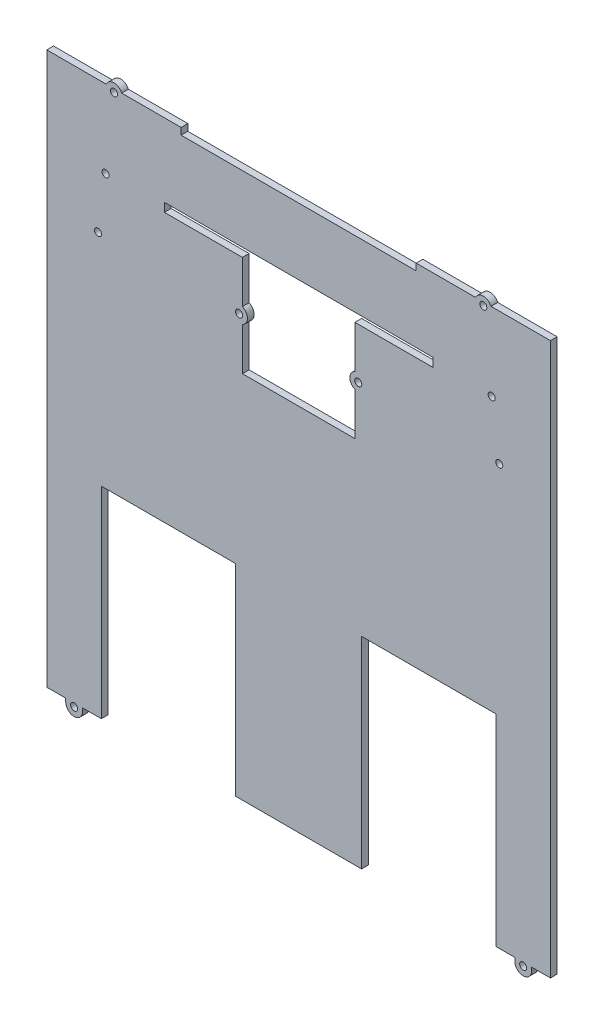
SolidWorks part; units mm, degrees
ref_plane "Plan de face" through (0, 0, 0) normal (0, 0, 1) x (1, 0, 0)
ref_plane "Plan de dessus" through (0, 0, 0) normal (0, 1, 0) x (1, 0, 0)
ref_plane "Plan de droite" through (0, 0, 0) normal (1, 0, 0) x (0, 0, -1)
sketch "Esquisse1" plane through (0, 0, 0) normal (0, 0, 1) x (1, 0, 0)
  line L1 (150, -140) -> (-150, -140)
  line L2 (150, -140) -> (150, 140)
  line L3 (150, 140) -> (-150, 140)
  line L4 (-150, -140) -> (-150, 140)
  line L5 (150, -140) -> (-150, 140) construction
  line L6 (150, 140) -> (-150, -140) construction
  point P0 (0, 0)
  dimension "D1" = 280
  dimension "D2" = 300
extrude "Boss.-Extru.1" add sketch "Esquisse1" along normal blind 4
sketch "Esquisse2" plane through (0, 0, 4) normal (0, 0, 1) x (1, 0, 0)
  line L0 (0, 0) -> (0, -140) construction
  line L1 (-150, -140) -> (150, -140) construction
  line L2 (117.5, -140) -> (117.5, -20)
  line L3 (-37.5, -140) -> (-117.5, -140)
  line L4 (-37.5, -140) -> (-37.5, -20)
  line L5 (-37.5, -20) -> (-117.5, -20)
  line L6 (-117.5, -140) -> (-117.5, -20)
  line L7 (37.5, -20) -> (117.5, -20)
  line L8 (37.5, -140) -> (37.5, -20)
  line L9 (37.5, -140) -> (117.5, -140)
  dimension "D1" = 80
  dimension "D2" = 37.5
  dimension "D3" = 120
extrude "Enlèv. mat.-Extru.1" cut sketch "Esquisse2" against normal through all
sketch "Esquisse4" plane through (0, 0, 0) normal (0, 0, -1) x (-1, 0, 0)
  line L0 (-150, 140) -> (150, 140) construction
  line L1 (-33.5, 140) -> (33.5, 140)
  line L2 (-33.5, 140) -> (-33.5, 80)
  line L3 (-33.5, 80) -> (33.5, 80)
  line L4 (33.5, 140) -> (33.5, 80)
  point P6 (0, 80)
  dimension "D1" = 60
  dimension "D2" = 67
extrude "Enlèv. mat.-Extru.3" cut sketch "Esquisse4" against normal through all
sketch "Esquisse5" plane through (0, 0, 0) normal (0, 0, -1) x (-1, 0, 0)
  line L0 (-133.75, -140) -> (-133.75, -147) construction
  line L1 (-117.5, -140) -> (-150, -140) construction
  line L2 (-128.75, -140) -> (-138.75, -140)
  line L3 (-138.75, -140) -> (-138.75, -142)
  line L4 (-128.75, -140) -> (-128.75, -142)
  line L5 (0, 0) -> (0, -140) construction
  line L6 (-37.5, -140) -> (37.5, -140) construction
  line L7 (133.75, -140) -> (133.75, -147) construction
  line L8 (128.75, -140) -> (128.75, -142)
  line L9 (138.75, -140) -> (138.75, -142)
  line L10 (128.75, -140) -> (138.75, -140)
  arc A0 (-138.75, -142) -> (-128.75, -142) centre (-133.75, -142) ccw
  arc A3 (138.75, -142) -> (128.75, -142) centre (133.75, -142) cw
  line M14 (-150, -140) -> (-117.5, -140)
  line M22 (117.5, -140) -> (150, -140)
  dimension "D2" = 5
  dimension "D3" = 2
extrude "Boss.-Extru.2" add sketch "Esquisse5" against normal blind 4 contours L3 A0 L4 M14 | A3 L9 L8 M22 region at (133.75, -143.0686, 0) region at (-133.75, -143.0686, 0)
sketch "Esquisse6" plane through (0, 0, 0) normal (0, 0, -1) x (-1, 0, 0)
  circle A0 centre (-133.75, -142) radius 2.1
  circle A1 centre (133.75, -142) radius 2.1
  dimension "D1" = 4.2
extrude "Enlèv. mat.-Extru.4" cut sketch "Esquisse6" against normal through all
sketch "Esquisse7" plane through (0, 0, 0) normal (0, 0, -1) x (-1, 0, 0)
  line L0 (-150, 140) -> (-150, 184.8)
  line L1 (-150, 184.8) -> (150, 184.8)
  line L2 (0, 184.8) -> (0, 145.2) construction
  line L3 (80, 145.2) -> (-80, 145.2)
  line L4 (-80, 145.2) -> (-80, 140)
  line L5 (-150, 140) -> (-33.5, 140) construction
  line L6 (-80, 140) -> (-150, 140)
  line L7 (-111.83, -155.2) -> (-81.83, -155.2) construction
  line L8 (80, 140) -> (150, 140)
  line L9 (80, 145.2) -> (80, 140)
  line L10 (150, 140) -> (150, 184.8)
  dimension "D1" = 5.2
  dimension "D2" = 70
  dimension "D3" = 340
extrude "Boss.-Extru.3" add sketch "Esquisse7" against normal blind 4
sketch "Esquisse8" plane through (0, 0, 0) normal (0, 0, -1) x (-1, 0, 0)
  line L0 (0, 184.8) -> (0, 0) construction
  line L1 (150, 184.8) -> (-150, 184.8) construction
  line L2 (-150, 184.8) -> (-150, 188.8)
  line L3 (-150, 188.8) -> (-114.5826, 188.8)
  line L4 (-70, 188.8) -> (-70, 184.8)
  line L5 (-70, 184.8) -> (-150, 184.8)
  line L6 (-105.4174, 188.8) -> (-70, 188.8)
  line L7 (105.4174, 188.8) -> (70, 188.8)
  line L8 (70, 184.8) -> (150, 184.8)
  line L9 (70, 188.8) -> (70, 184.8)
  line L10 (150, 188.8) -> (114.5826, 188.8)
  line L11 (150, 184.8) -> (150, 188.8)
  arc A0 (-114.5826, 188.8) -> (-105.4174, 188.8) centre (-110, 186.8) cw
  arc A1 (114.5826, 188.8) -> (105.4174, 188.8) centre (110, 186.8) ccw
  point P16 (-110, 184.8)
  dimension "D1" = 4
  dimension "D3" = 5
  dimension "D2" = 2
  dimension "D4" = 40
extrude "Boss.-Extru.4" add sketch "Esquisse8" against normal blind 4
sketch "Esquisse9" plane through (0, 0, 0) normal (0, 0, -1) x (-1, 0, 0)
  circle A0 centre (-110, 186.8) radius 2.1
  circle A1 centre (110, 186.8) radius 2.1
  dimension "D1" = 4.2
extrude "Enlèv. mat.-Extru.5" cut sketch "Esquisse9" against normal through all
sketch "Esquisse10" plane through (0, 0, 0) normal (0, 0, -1) x (-1, 0, 0)
  line L0 (80, 142.5) -> (150, 142.5) construction
  line L1 (80, 145.2) -> (80, 140) construction
  line L2 (150, 188.8) -> (150, -140) construction
  line L3 (0, 0) -> (0, 80) construction
  line L4 (-33.5, 80) -> (33.5, 80) construction
  line L5 (33.5, 140) -> (80, 140) construction
  line L6 (-80, 142.5) -> (-150, 142.5) construction
  circle A0 centre (115, 142.5) radius 2.1
  circle A1 centre (-115, 142.5) radius 2.1
  dimension "D1" = 2.5
  dimension "D2" = 4.2
extrude "Enlèv. mat.-Extru.6" cut sketch "Esquisse10" against normal through all
sketch "Esquisse11" plane through (0, 0, 4) normal (0, 0, 1) x (1, 0, 0)
  line L0 (37.5, 112.1) -> (33.5, 107.9) construction
  line L1 (37.5, 107.9) -> (33.5, 107.9) construction
  line L2 (33.5, 140) -> (33.5, 80) construction
  line L3 (37.5, 107.9) -> (33.5, 112.1) construction
  line L4 (37.5, 112.1) -> (33.5, 112.1) construction
  line L5 (121.5, 112.1) -> (117.5, 107.9) construction
  line L6 (117.5, 112.1) -> (121.5, 107.9) construction
  line L7 (121.5, 112.1) -> (117.5, 112.1) construction
  line L8 (0, 0) -> (0, 80) construction
  line L9 (33.5, 80) -> (-33.5, 80) construction
  line L10 (-117.5, 112.1) -> (-121.5, 107.9) construction
  line L11 (-121.5, 112.1) -> (-117.5, 107.9) construction
  line L12 (-37.5, 107.9) -> (-33.5, 112.1) construction
  line L13 (-37.5, 112.1) -> (-33.5, 107.9) construction
  circle A0 centre (35.5, 110) radius 2.1
  circle A1 centre (119.5, 110) radius 2.1
  circle A2 centre (-119.5, 110) radius 2.1
  circle A3 centre (-35.5, 110) radius 2.1
  dimension "D1" = 4.2
extrude "Enlèv. mat.-Extru.7" cut sketch "Esquisse11" against normal through all
sketch "Esquisse12" plane through (0, 0, 0) normal (0, 0, -1) x (-1, 0, 0)
  line L0 (0, 0) -> (0, 80) construction
  line L1 (-33.5, 80) -> (33.5, 80) construction
  circle A0 centre (-35.5, 110) radius 2.1
  circle A1 centre (-35.5, 110) radius 5
  circle A2 centre (35.5, 110) radius 5
  circle A3 centre (35.5, 110) radius 2.1
  dimension "D1" = 4.2
  dimension "D2" = 10
extrude "Boss.-Extru.5" add sketch "Esquisse12" against normal blind 4
